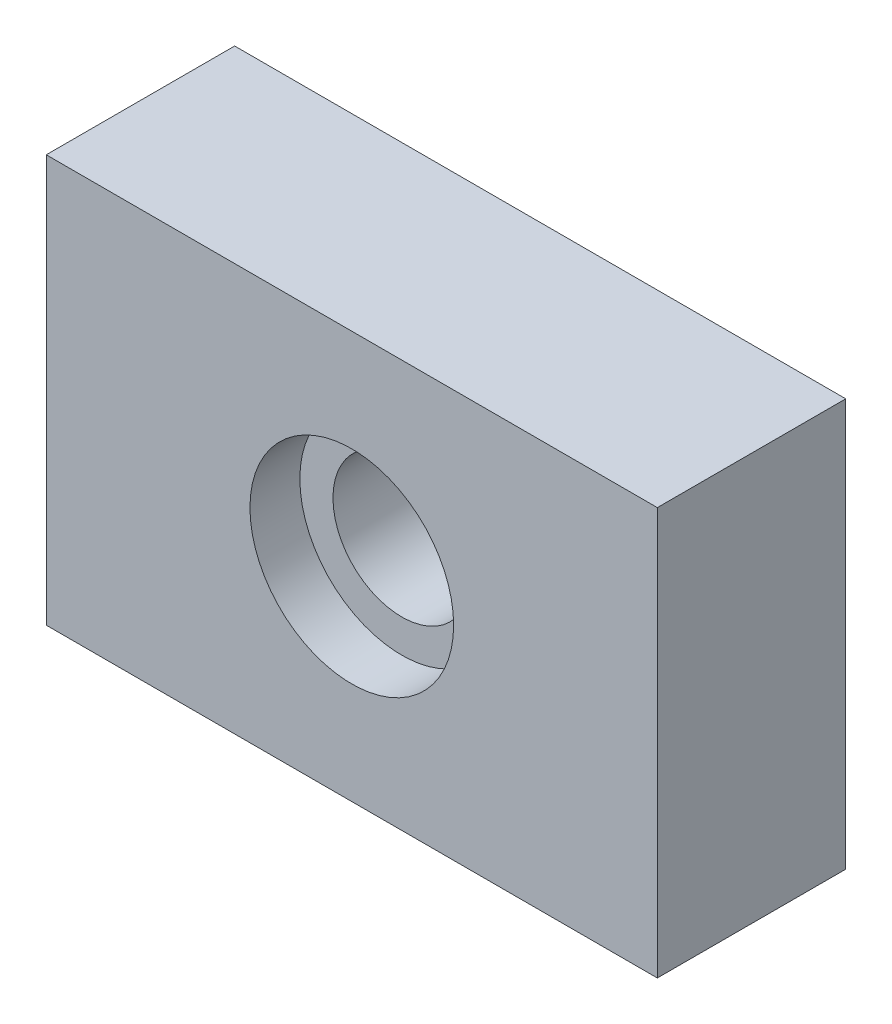
SolidWorks part; units mm, degrees
ref_plane "Front Plane" through (0, 0, 0) normal (0, 0, 1) x (1, 0, 0)
ref_plane "Top Plane" through (0, 0, 0) normal (0, 1, 0) x (1, 0, 0)
ref_plane "Right Plane" through (0, 0, 0) normal (1, 0, 0) x (0, 0, -1)
sketch "Sketch1" plane through (0, 0, 0) normal (0, 0, 1) x (1, 0, 0)
  line L1 (0, 0) -> (152.4, 0)
  line L2 (0, 0) -> (0, 101.6)
  line L3 (0, 101.6) -> (152.4, 101.6)
  line L4 (152.4, 0) -> (152.4, 101.6)
  dimension "D1" = 152.4
  dimension "D2" = 101.6
extrude "Boss-Extrude1" add sketch "Sketch1" along normal blind 46.99
sketch "Sketch2" plane through (0, 0, 0) normal (0, 0, -1) x (-1, 0, 0)
  line L0 (0, 50.8) -> (-152.4, 50.8) construction
  line L1 (0, 101.6) -> (0, 0) construction
  line L2 (-152.4, 0) -> (-152.4, 101.6) construction
  line L4 (-152.4, 101.6) -> (0, 101.6) construction
  line L5 (-76.2, 101.6) -> (-76.2, 0) construction
  line L6 (0, 0) -> (-152.4, 0) construction
  circle A0 centre (-76.2, 50.8) radius 25.4
  circle A1 centre (-76.2, 50.8) radius 17.145
  dimension "D1" = 50.8
  dimension "D2" = 34.29
extrude "Cut-Extrude1" cut sketch "Sketch2" against normal through all contours A1
extrude "Cut-Extrude3" cut sketch "Sketch2<2>" against normal blind 12.446
sketch "Sketch2<2>" plane through (0, 0, 0) normal (0, 0, -1) x (-1, 0, 0) same geometry as "Sketch2"
ref_plane "Plane2" through (0, 0, 23.495) normal (0, 0, -1) x (-1, 0, 0)
mirror "Mirror2" about plane through (0, 0, 23.495) normal (0, 0, -1) of "Cut-Extrude3"
equation "\"through_diamiter\"= 1.35"
equation "\"D2@Sketch2\"= \"through_diamiter\""
equation "\"bearing depth\"= 0.5"
